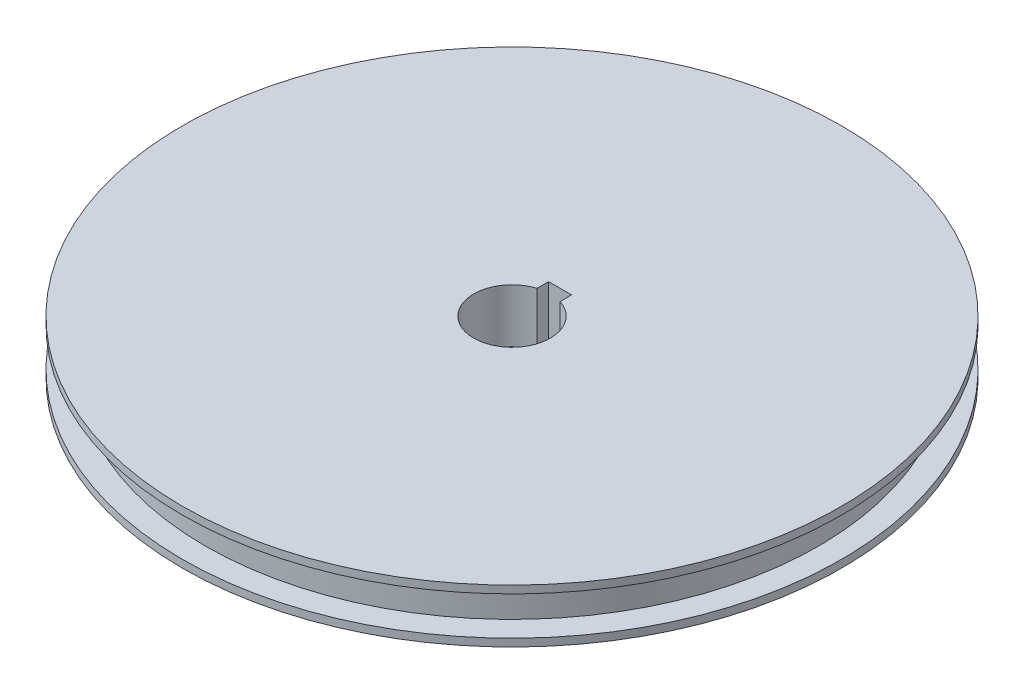
SolidWorks part; units mm, degrees
material "Nylon 101"
ref_plane "Front Plane" through (0, 0, 0) normal (0, 0, 1) x (1, 0, 0)
ref_plane "Top Plane" through (0, 0, 0) normal (0, 1, 0) x (1, 0, 0)
ref_plane "Right Plane" through (0, 0, 0) normal (1, 0, 0) x (0, 0, -1)
sketch "Sketch1" plane through (0, 0, 0) normal (0, 1, 0) x (1, 0, 0)
  line L0 (0, 0) -> (0, 22.1757) construction
  line L3 (-1.5, 4.7697) -> (-1.5, 6.2697)
  line L4 (-1.5, 6.2697) -> (1.5, 6.2697)
  line L5 (1.5, 4.7697) -> (1.5, 6.2697)
  circle A0 centre (0, 0) radius 5
  circle A1 centre (0, 0) radius 40
  circle A2 centre (0, 0) radius 43
  point P10 (0, 0)
  point P11 (1.3088, 4.8257)
  dimension "D1" = 80
  dimension "D2" = 10
  dimension "D3" = 3
  dimension "D4" = 1.5
  dimension "D5" = 3
extrude "Boss-Extrude1" add sketch "Sketch1" along normal blind 5 contours A1 A0 region at (-38.8686, 0, 0)
extrude "Boss-Extrude2" add sketch "Sketch1<3>" against normal blind 1 contours A1 A0 | A2 A1 region at (-38.8686, 0, 0) region at (-41.7838, 0, 0)
sketch "Sketch1<3>" plane through (0, 0, 0) normal (0, 1, 0) x (1, 0, 0) same geometry as "Sketch1"
extrude "Boss-Extrude3" add sketch "Sketch1<4>" along normal blind 1 from surface contours A1 A0 | A2 A1 region at (-38.8686, 0, 0) region at (-41.7838, 0, 0) starting at face at (0, 5, -3.0773)
sketch "Sketch1<4>" plane through (0, 0, 0) normal (0, 1, 0) x (1, 0, 0) same geometry as "Sketch1"
